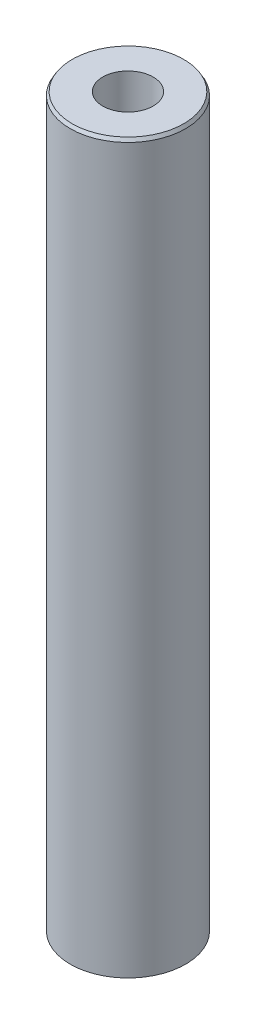
SolidWorks part; units mm, degrees
ref_plane "Front Plane" through (0, 0, 0) normal (0, 0, 1) x (1, 0, 0)
ref_plane "Top Plane" through (0, 0, 0) normal (0, 1, 0) x (1, 0, 0)
ref_plane "Right Plane" through (0, 0, 0) normal (1, 0, 0) x (0, 0, -1)
sketch "Sketch1" plane through (0, 0, 0) normal (0, 1, 0) x (1, 0, 0)
  circle A0 centre (0, 0) radius 47.5
  dimension "SHAFT_OD" = 95
extrude "Boss-Extrude1" add sketch "Sketch1" along normal blind 600
sketch "Sketch2" plane through (0, 0, 0) normal (0, 1, 0) x (1, 0, 0)
  circle A0 centre (0, 0) radius 20.7554
  dimension "BORE_D" = 41.5108
extrude "Cut-Extrude1" cut sketch "Sketch2" along normal through all
chamfer "Chamfer1" distance 2.747 angle 30 2 edges at (0, 600, 47.5) (0, 0, 47.5) first distance on face at (0, 600, 47.5) first distance on face at (0, 0, 20.7554)
